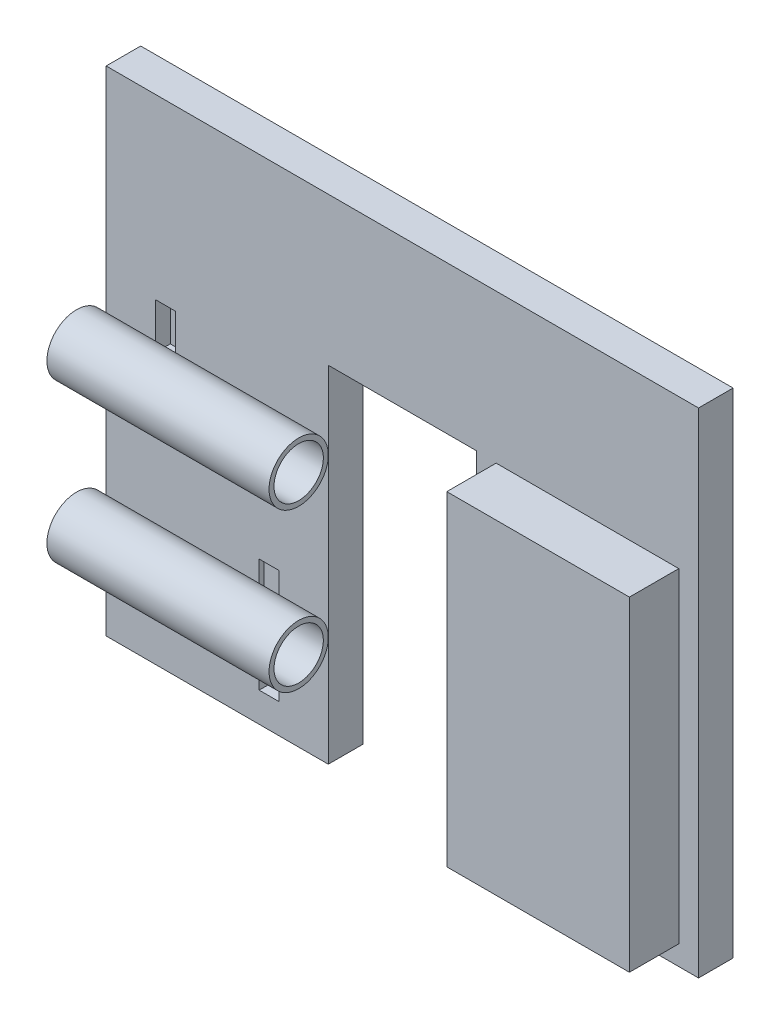
SolidWorks part; units mm, degrees
ref_plane "Front Plane" through (0, 0, 0) normal (0, 0, 1) x (1, 0, 0)
ref_plane "Top Plane" through (0, 0, 0) normal (0, 1, 0) x (1, 0, 0)
ref_plane "Right Plane" through (0, 0, 0) normal (1, 0, 0) x (0, 0, -1)
sketch "Sketch2" plane through (0, 0, 0) normal (0, 0, 1) x (1, 0, 0)
  line L1 (0, 0) -> (120, 0)
  line L2 (0, 0) -> (0, -100)
  line L3 (0, -100) -> (120, -100)
  line L4 (120, 0) -> (120, -100)
  dimension "D1" = 120
  dimension "D2" = 100
extrude "Boss-Extrude1" add sketch "Sketch2" along normal blind 7
ref_axis "Axis1" through (60, 0, 7) along (0, -1, 0)
ref_plane "Plane1" through (60, 0, 0) normal (1, 0, 0) x (0, 0, -1)
sketch "Sketch4" plane through (0, 0, 7) normal (0, 0, 1) x (1, 0, 0)
  line L0 (60, 0) -> (60, -100) construction
  line L1 (75, -100) -> (45, -100)
  line L2 (60, -100) -> (60, -30)
  line L3 (75, -30) -> (45, -30)
  line L4 (45, -100) -> (45, -30)
  line L5 (0, -100) -> (120, -100) construction
  line L6 (60, -55) -> (60, 55) construction
  line L7 (75, -100) -> (75, -30)
  dimension "D1" = 15
  dimension "D2" = 70
extrude "Cut-Extrude1" cut sketch "Sketch4" against normal blind 10 contours L3 L4 L1 L7
ref_plane "Plane2" through (45, 0, 0) normal (-1, 0, 0) x (0, 0, 1)
sketch "Sketch5" plane through (0, 0, 0) normal (1, 0, 0) x (0, 0, -1)
  line L0 (0, 0) -> (0, -100) construction
  circle A0 centre (-13, -45.754) radius 6
  dimension "D1" = 13
extrude "Boss-Extrude2" add sketch "Sketch5" along normal blind 45 separate body contours A0
ref_point "Point1"
sketch "Sketch8" plane through (0, 0, 0) normal (-1, 0, 0) x (0, 0, 1)
  circle A0 centre (13, -45.754) radius 5
extrude "Cut-Extrude2" cut sketch "Sketch8" against normal blind 45
sketch "Sketch10" plane through (0, 0, 7) normal (0, 0, 1) x (1, 0, 0)
  line L0 (75, -30) -> (45, -30) construction
  line L1 (10, -36) -> (14, -36)
  line L2 (10, -36) -> (10, -59)
  line L3 (10, -59) -> (14, -59)
  line L4 (14, -36) -> (14, -59)
  line L5 (0, -100) -> (45, -100) construction
  line L6 (0, 0) -> (0, -100) construction
  line L7 (45, -100) -> (45, -30) construction
  line L8 (30.9997, -71) -> (34.9997, -71)
  line L9 (30.9997, -71) -> (30.9997, -94)
  line L10 (30.9997, -94) -> (34.9997, -94)
  line L11 (34.9997, -71) -> (34.9997, -94)
  dimension "D1" = 6
  dimension "D2" = 41
  dimension "D3" = 4
  dimension "D4" = 10
  dimension "D5" = 6
  dimension "D6" = 41
  dimension "D7" = 10.0003
  dimension "D8" = 4
extrude "Cut-Extrude4" cut sketch "Sketch10" against normal blind 3
sketch "Sketch12" plane through (0, -59, 0) normal (0, 1, 0) x (1, 0, 0)
  line L0 (14, -4) -> (14, -7) construction
  line L1 (10, -4) -> (14, -4)
  line L2 (10, -4) -> (10, -6)
  line L3 (10, -6) -> (14, -6)
  line L4 (14, -4) -> (14, -6)
  line L5 (10, -7) -> (14, -7) construction
  dimension "D1" = 1
extrude "Cut-Extrude5" cut sketch "Sketch12" against normal blind 39
sketch "Sketch13" plane through (0, -71, 0) normal (0, -1, 0) x (1, 0, 0)
  line L0 (30.9997, 4) -> (30.9997, 7) construction
  line L1 (34.9997, 4) -> (30.9997, 4)
  line L2 (34.9997, 4) -> (34.9997, 6.0022)
  line L3 (34.9997, 6.0022) -> (30.9997, 6.0022)
  line L4 (30.9997, 4) -> (30.9997, 6.0022)
  line L5 (34.9997, 7) -> (30.9997, 7) construction
  point P7 (32.9997, 6.0022)
  dimension "D1" = 0.9978
extrude "Cut-Extrude6" cut sketch "Sketch13" against normal blind 39
ref_plane "Plane3" through (10, 0, 0) normal (-1, 0, 0) x (0, 0, 1)
ref_axis "Axis2" through (0, -45.754, -32.2143) along (0, 0, 1)
ref_plane "Plane4" through (0, -45.754, 0) normal (0, -1, 0) x (0, 0, 1)
sketch "Sketch15" plane through (10, 0, 0) normal (-1, 0, 0) x (0, 0, 1)
  line L0 (-32.2143, -45.754) -> (59.669, -45.754) construction
  line L1 (8, -45.754) -> (4, -45.754)
  line L2 (8, -45.754) -> (8, -45.254)
  line L3 (8, -45.254) -> (4, -45.254)
  line L4 (4, -45.754) -> (4, -45.254)
  circle A0 centre (13, -45.754) radius 5 construction
  dimension "D1" = 4
  dimension "D2" = 0.5
extrude "Boss-Extrude4" add sketch "Sketch15" against normal blind 4 separate body
sketch "Sketch17" plane through (10, 0, 0) normal (-1, 0, 0) x (0, 0, 1)
  line L0 (-50.5358, -45.754) -> (50.5358, -45.754) construction
  line L1 (4, -45.754) -> (6, -45.754)
  line L2 (4, -45.754) -> (4, -84.754)
  line L3 (4, -84.754) -> (6, -84.754)
  line L4 (6, -45.754) -> (6, -84.754)
  line L5 (7, 0) -> (7, -100) construction
  dimension "D1" = 1
  dimension "D2" = 2
  dimension "D3" = 39
extrude "Boss-Extrude7" add sketch "Sketch17" against normal blind 4
ref_plane "Plane5" through (0, -77.754, 0) normal (0, -1, 0) x (0, 0, 1)
ref_plane "Plane6" through (30.9997, 0, 0) normal (1, 0, 0) x (0, 0, -1)
sketch "Sketch21" plane through (30.9997, 0, 0) normal (1, 0, 0) x (0, 0, -1)
  line L0 (-50.5358, -77.754) -> (50.5358, -77.754) construction
  line L1 (-6, -77.754) -> (-10, -77.754)
  line L2 (-6, -77.754) -> (-6, -78.254)
  line L3 (-6, -78.254) -> (-10, -78.254)
  line L4 (-10, -77.754) -> (-10, -78.254)
  line L5 (-7, 0) -> (-7, -100) construction
  dimension "D1" = 0.5
  dimension "D2" = 1
  dimension "D3" = 3
extrude "Boss-Extrude8" add sketch "Sketch21" along normal blind 4
sketch "Sketch23" plane through (30.9997, 0, 0) normal (1, 0, 0) x (0, 0, -1)
  line L0 (-50.5358, -77.754) -> (50.5358, -77.754) construction
  line L1 (-6, -77.754) -> (-4, -77.754)
  line L2 (-6, -77.754) -> (-6, -38.754)
  line L3 (-6, -38.754) -> (-4, -38.754)
  line L4 (-4, -77.754) -> (-4, -38.754)
  line L5 (-7, -100) -> (-7, 0) construction
  dimension "D1" = 1
  dimension "D2" = 2
  dimension "D3" = 39
extrude "Boss-Extrude11" add sketch "Sketch23" along normal blind 4 separate body
sketch "Sketch24" plane through (0, 0, 0) normal (1, 0, 0) x (0, 0, -1)
  line L0 (-50.5358, -77.754) -> (50.5358, -77.754) construction
  line L1 (0, -100) -> (0, 0) construction
  circle A0 centre (-13, -77.754) radius 6
  dimension "D1" = 13
extrude "Boss-Extrude13" add sketch "Sketch24" along normal blind 45 separate body
ref_point "Point2"
sketch "Sketch25" plane through (45, 0, 0) normal (1, 0, 0) x (0, 0, -1)
  circle A0 centre (-13, -77.754) radius 5
extrude "Cut-Extrude7" cut sketch "Sketch25" against normal blind 45
sketch "Sketch28" plane through (0, 0, 7) normal (0, 0, 1) x (1, 0, 0)
  line L0 (75, -100) -> (75, -30) construction
  line L1 (79, -30.1767) -> (116, -30.1767)
  line L2 (79, -30.1767) -> (79, -96)
  line L3 (79, -96) -> (116, -96)
  line L4 (116, -30.1767) -> (116, -96)
  line L5 (120, -100) -> (120, 0) construction
  line L6 (75, -100) -> (120, -100) construction
  dimension "D1" = 4
  dimension "D2" = 4
  dimension "D3" = 4
extrude "Boss-Extrude15" add sketch "Sketch28" along normal blind 10 contours L2 L1 L4 L3
sketch "Sketch30" plane through (79, 0, 0) normal (-1, 0, 0) x (0, 0, 1)
  line L0 (17, -30.1767) -> (7, -30.1767) construction
  line L1 (15.5, -31.6767) -> (8.5, -31.6767)
  line L2 (15.5, -31.6767) -> (15.5, -94.5)
  line L3 (15.5, -94.5) -> (8.5, -94.5)
  line L4 (8.5, -31.6767) -> (8.5, -94.5)
  line L5 (17, -96) -> (7, -96) construction
  line L6 (17, -30.1767) -> (17, -96) construction
  line L7 (7, -30.1767) -> (7, -96) construction
  dimension "D1" = 1.5
  dimension "D2" = 1.5
  dimension "D3" = 1.5
  dimension "D4" = 1.5
extrude "Cut-Extrude8" cut sketch "Sketch30" against normal blind 36.5
